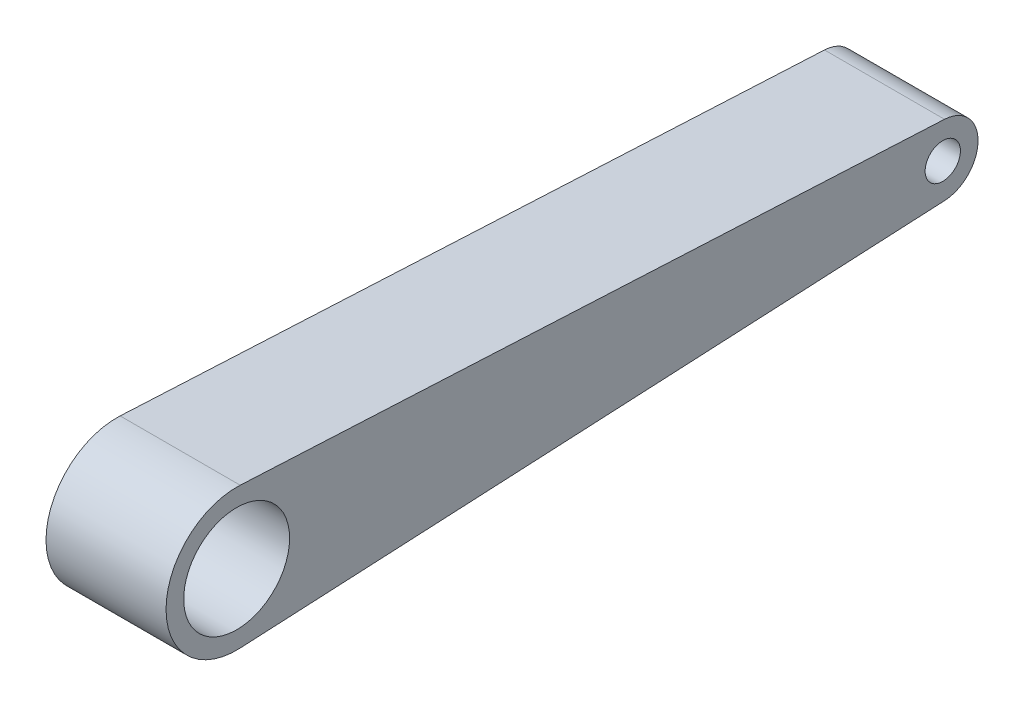
SolidWorks part; units mm, degrees
ref_plane "Front Plane" through (0, 0, 0) normal (0, 0, 1) x (1, 0, 0)
ref_plane "Top Plane" through (0, 0, 0) normal (0, 1, 0) x (1, 0, 0)
ref_plane "Right Plane" through (0, 0, 0) normal (1, 0, 0) x (0, 0, -1)
sketch "Profile Sketch" plane through (0, 0, 0) normal (1, 0, 0) x (0, 0, -1)
  line L0 (-199, 19.975) -> (0.5, 9.9875)
  line L1 (-199, -19.975) -> (0.5, -9.9875)
  line L2 (-200, 0) -> (0, 0) construction
  arc A0 (0.5, -9.9875) -> (0.5, 9.9875) centre (0, 0) ccw
  arc A1 (-199, 19.975) -> (-199, -19.975) centre (-200, 0) ccw
  circle A2 centre (-200, 0) radius 20 construction
  circle A3 centre (0, 0) radius 10 construction
  dimension "D1" = 40
  dimension "D2" = 20
  dimension "D3" = 200
extrude "Profile Extrude" add sketch "Profile Sketch" along normal blind 34
sketch "Holes Sketch" plane through (34, 0, 0) normal (1, 0, 0) x (0, 0, -1)
  circle A0 centre (0, 0) radius 5
  circle A1 centre (-200, 0) radius 15
  arc A2 (0.5, -9.9875) -> (0.5, 9.9875) centre (0, 0) ccw construction
  arc A3 (-199, 19.975) -> (-199, -19.975) centre (-200, 0) ccw construction
  dimension "D1" = 10
  dimension "D2" = 30
extrude "Holes Cut" cut sketch "Holes Sketch" against normal up to surface (34 mm away) up to face at (0, 0, 102.125)
